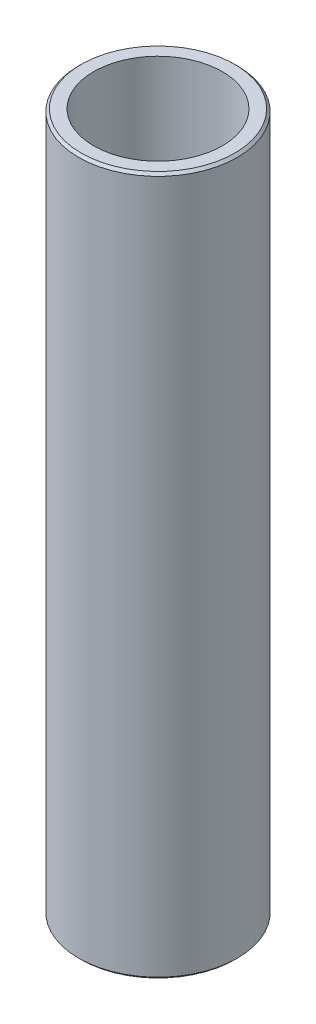
SolidWorks part; units mm, degrees
ref_plane "Front Plane" through (0, 0, 0) normal (0, 0, 1) x (1, 0, 0)
ref_plane "Top Plane" through (0, 0, 0) normal (0, 1, 0) x (1, 0, 0)
ref_plane "Right Plane" through (0, 0, 0) normal (1, 0, 0) x (0, 0, -1)
sketch "Sketch1" plane through (0, 0, 0) normal (0, 1, 0) x (1, 0, 0)
  circle A0 centre (0, 0) radius 7.94
  circle A1 centre (0, 0) radius 6.44
  dimension "D1" = 15.88
  dimension "D2" = 1.5
extrude "Boss-Extrude1" add sketch "Sketch1" along normal blind 69.91
chamfer "Chamfer1" distance 0.25 angle 45 2 edges at (0, 0, 7.94) (0, 69.91, 7.94)
